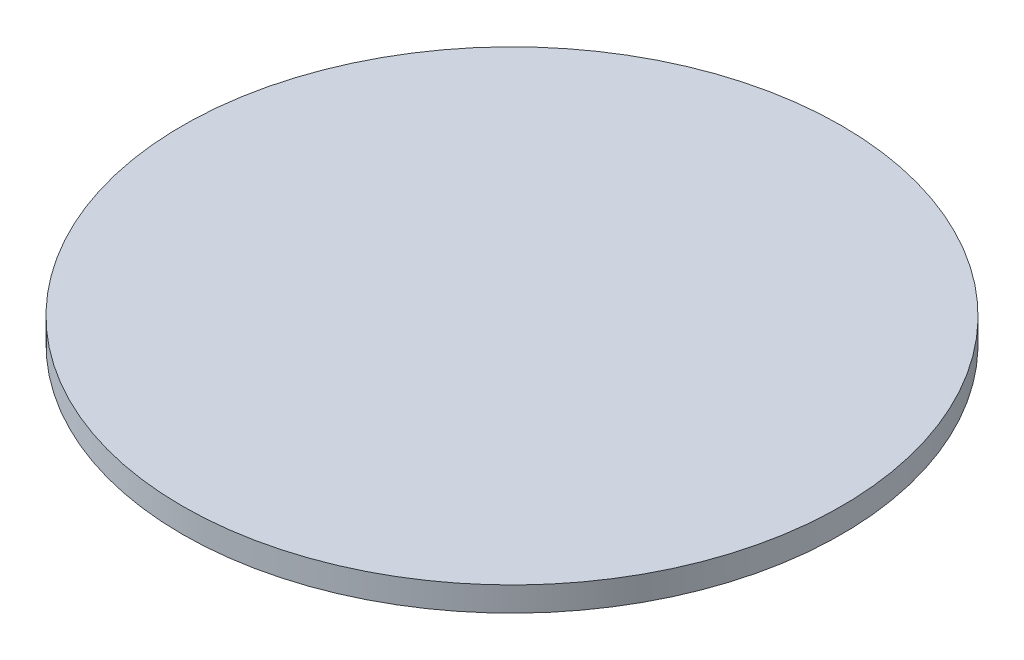
SolidWorks part; units mm, degrees
ref_plane "Front Plane" through (0, 0, 0) normal (0, 0, 1) x (1, 0, 0)
ref_plane "Top Plane" through (0, 0, 0) normal (0, 1, 0) x (1, 0, 0)
ref_plane "Right Plane" through (0, 0, 0) normal (1, 0, 0) x (0, 0, -1)
sketch "Sketch1" plane through (0, 0, 0) normal (0, 1, 0) x (1, 0, 0)
  circle A0 centre (0, 0) radius 34.2609
extrude "Boss-Extrude1" add sketch "Sketch1" along normal blind 2.54
